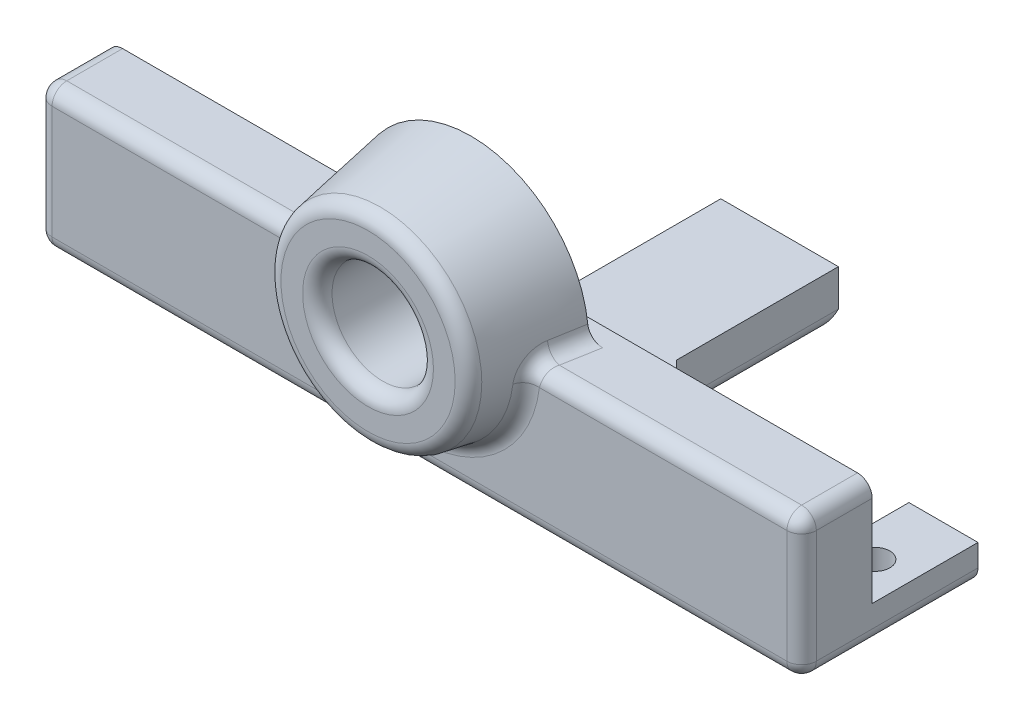
SolidWorks part; units mm, degrees
ref_plane "Front Plane" through (0, 0, 0) normal (0, 0, 1) x (1, 0, 0)
ref_plane "Top Plane" through (0, 0, 0) normal (0, 1, 0) x (1, 0, 0)
ref_plane "Right Plane" through (0, 0, 0) normal (1, 0, 0) x (0, 0, -1)
sketch "Sketch1" plane through (0, 0, 0) normal (0, 0, 1) x (1, 0, 0)
  line L1 (-26, -4.85) -> (26, -4.85)
  line L2 (-26, -4.85) -> (-26, 4.85)
  line L3 (-26, 4.85) -> (26, 4.85)
  line L4 (26, -4.85) -> (26, 4.85)
  line L5 (-26, -4.85) -> (26, 4.85) construction
  line L6 (-26, 4.85) -> (26, -4.85) construction
  point P0 (0, 0)
  dimension "D1" = 52
  dimension "D2" = 9.7
extrude "Boss-Extrude1" add sketch "Sketch1" along normal blind 4.8
sketch "Sketch2" plane through (0, -4.85, 0) normal (0, -1, 0) x (1, 0, 0)
  line L0 (-26, 0) -> (26, 0) construction
  line L1 (-26, 0) -> (-21.3, 0)
  line L2 (-26, 0) -> (-26, -7.2)
  line L3 (-26, -7.2) -> (-21.3, -7.2)
  line L4 (-21.3, 0) -> (-21.3, -7.2)
  line L5 (-26, 4.8) -> (-26, 0) construction
  line L6 (26, 0) -> (21.3, 0)
  line L7 (26, 0) -> (26, -7.2)
  line L8 (26, -7.2) -> (21.3, -7.2)
  line L9 (21.3, 0) -> (21.3, -7.2)
  dimension "D1" = 7.2
  dimension "D2" = 4.7
extrude "Boss-Extrude2" add sketch "Sketch2" against normal blind 2.5
sketch "Sketch3" plane through (0, 0, 4.8) normal (0, 0, 1) x (1, 0, 0)
  line L0 (26, 4.85) -> (-26, 4.85) construction
  circle A0 centre (0, 4.85) radius 8
  dimension "D1" = 16
extrude "Boss-Extrude3" add sketch "Sketch3" along normal blind 7 draft 10 from offset 3.5 offset against normal yes
sketch "Sketch4" plane through (0, 0, 8.3) normal (0, 0, 1) x (1, 0, 0)
  circle A0 centre (0, 4.85) radius 3.45
  dimension "D1" = 6.9
extrude "Cut-Extrude1" cut sketch "Sketch4" against normal through all
sketch "Sketch5" plane through (0, -4.85, 0) normal (0, -1, 0) x (1, 0, 0)
  line L1 (-10.65, 4.8) -> (10.65, 4.8)
  line L2 (-10.65, 4.8) -> (-10.65, -1.7)
  line L4 (10.65, 4.8) -> (10.65, -1.7)
  line L5 (0, 0) -> (0, -50000) construction
  line L6 (-21.3, 0) -> (21.3, 0) construction
  line L7 (-10.65, -1.7) -> (-4, -8.7)
  line L8 (-4, -8.7) -> (-4, -19.7)
  line L9 (-4, -19.7) -> (4, -19.7)
  line L10 (4, -8.7) -> (4, -19.7)
  line L11 (10.65, -1.7) -> (4, -8.7)
  line L12 (-26, 4.8) -> (26, 4.8) construction
  point P12 (0, 0)
  point P17 (0, -19.7)
  dimension "D1" = 21.3
  dimension "D2" = 6.5
  dimension "D3" = 13.5
  dimension "D4" = 4
  dimension "D5" = 11
extrude "Boss-Extrude4" add sketch "Sketch5" along normal blind 1.5 from offset 1.5 offset against normal yes
sketch "Sketch6" plane through (0, -4.85, 0) normal (0, -1, 0) x (1, 0, 0)
  line L0 (-26, 4.8) -> (26, 4.8) construction
  line L1 (-4, -19.7) -> (-4, -7.2)
  line L2 (4, -19.7) -> (4, -7.2)
  line L3 (-4, -19.7) -> (4, -19.7)
  arc A0 (4, -7.2) -> (-4, -7.2) centre (0, -4.2) ccw
  dimension "D2" = 10
  dimension "D1" = 9
extrude "Boss-Extrude5" add sketch "Sketch6" along normal blind 2
sketch "Sketch7" plane through (0, -6.85, 0) normal (0, -1, 0) x (1, 0, 0)
  circle A0 centre (0, -4.2) radius 3.25
  dimension "D1" = 6.5
extrude "Cut-Extrude2" cut sketch "Sketch7" against normal through all
chamfer "Chamfer1" distance 1 angle 45 1 edges at (0, -6.85, -19.7)
fillet "Fillet2" radius 1 21 edges at (-7.6914, 4.85, 3.05) (7.6914, 4.85, 3.05) (-26, 0, 4.8) (-16.6914, 4.85, 4.8) (0, -2.5329, 4.8) (16.6914, 4.85, 4.8) (26, 0, 4.8) (0, -4.85, 4.8) (6.7657, 4.85, 8.3) (3.45, 4.85, 8.3) (7.325, -4.85, -5.2) (10.65, -4.85, -0.85) (-10.65, -4.85, -0.85) (-7.325, -4.85, -5.2) (-4, -6.85, -12.95) (4, -6.85, -12.95) (0, -6.85, 0.8) (-26, -4.85, -1.2) (26, -4.85, -1.2) (26, 4.85, 2.4) (-26, 4.85, 2.4)
sketch "Sketch8" plane through (0, -2.35, 0) normal (0, 1, 0) x (1, 0, 0)
  line L0 (-8.1609, -4.8) -> (-25, -4.8) construction
  line L3 (0, 0) -> (0, -50000) construction
  circle A0 centre (-23.5, 2.7) radius 1
  circle A1 centre (23.5, 2.7) radius 1
  dimension "D2" = 2
  dimension "D1" = 7.5
  dimension "D3" = 47
extrude "Cut-Extrude3" cut sketch "Sketch8" against normal through all
